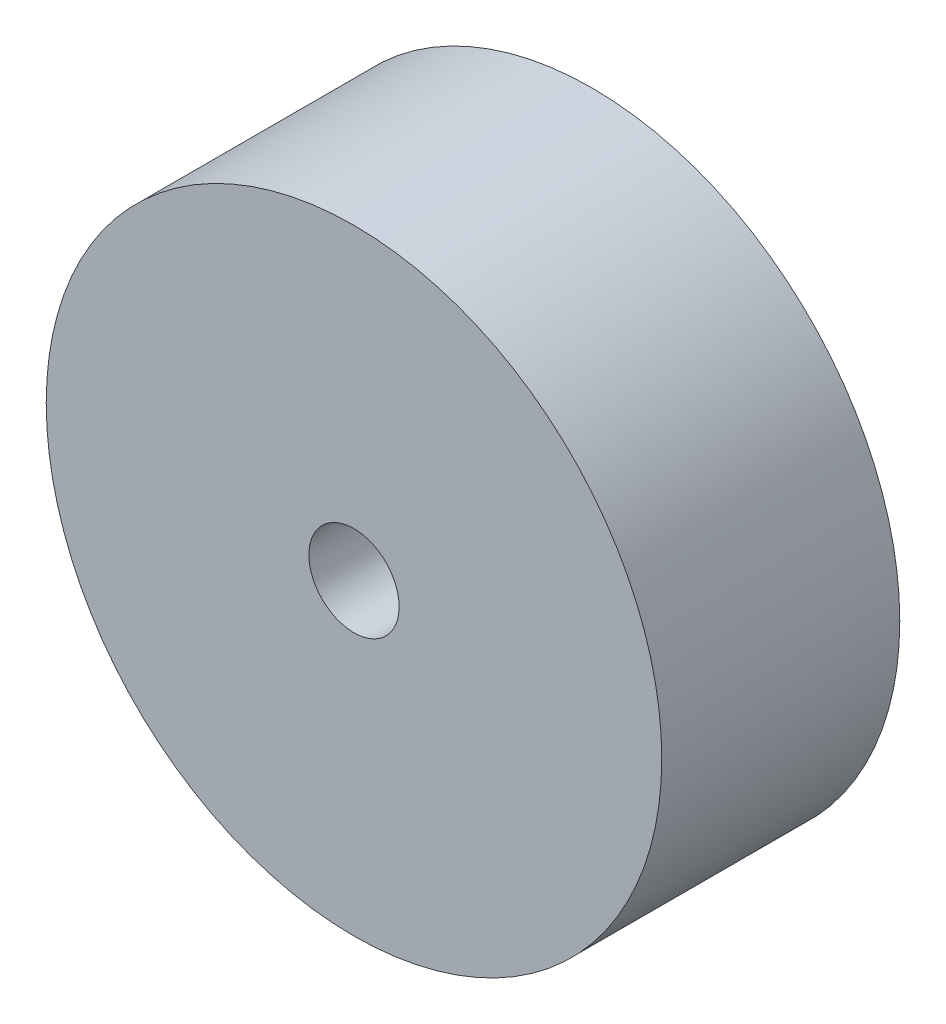
SolidWorks part; units mm, degrees
ref_plane "Front Plane" through (0, 0, 0) normal (0, 0, 1) x (1, 0, 0)
ref_plane "Top Plane" through (0, 0, 0) normal (0, 1, 0) x (1, 0, 0)
ref_plane "Right Plane" through (0, 0, 0) normal (1, 0, 0) x (0, 0, -1)
sketch "Sketch1" plane through (0, 0, 0) normal (0, 0, 1) x (1, 0, 0)
  circle A0 centre (-29.0823, -1.7038) radius 7.5
  dimension "D1" = 15
extrude "Boss-Extrude1" add sketch "Sketch1" along normal blind 5.8
sketch "Sketch2" plane through (0, 0, 0) normal (0, 0, -1) x (-1, 0, 0)
  circle A0 centre (29.0823, -1.7038) radius 6.4
  dimension "D1" = 12.8
extrude "Cut-Extrude1" cut sketch "Sketch2" against normal blind 1.5875
sketch "Sketch3" plane through (0, 0, 1.5875) normal (0, 0, -1) x (-1, 0, 0)
  circle A0 centre (29.0823, -1.7038) radius 1
  dimension "D1" = 2
extrude "Boss-Extrude2" add sketch "Sketch3" along normal blind 1.5875
sketch "Sketch4" plane through (0, 0, 0) normal (0, 0, -1) x (-1, 0, 0)
  circle A0 centre (29.0823, -1.7038) radius 1.5
  dimension "D1" = 3
extrude "Boss-Extrude3" add sketch "Sketch4" against normal blind 3
sketch "Sketch5" plane through (0, 0, 0) normal (0, 0, -1) x (-1, 0, 0)
  circle A0 centre (29.0823, -1.7038) radius 0.85
  dimension "D1" = 1.7
extrude "Cut-Extrude2" cut sketch "Sketch5" against normal through all
sketch "Sketch6" plane through (0, 0, 5.8) normal (0, 0, 1) x (1, 0, 0)
  circle A0 centre (-29.0823, -1.7038) radius 1.1
  dimension "D1" = 2.2
extrude "Cut-Extrude3" cut sketch "Sketch6" against normal blind 3
